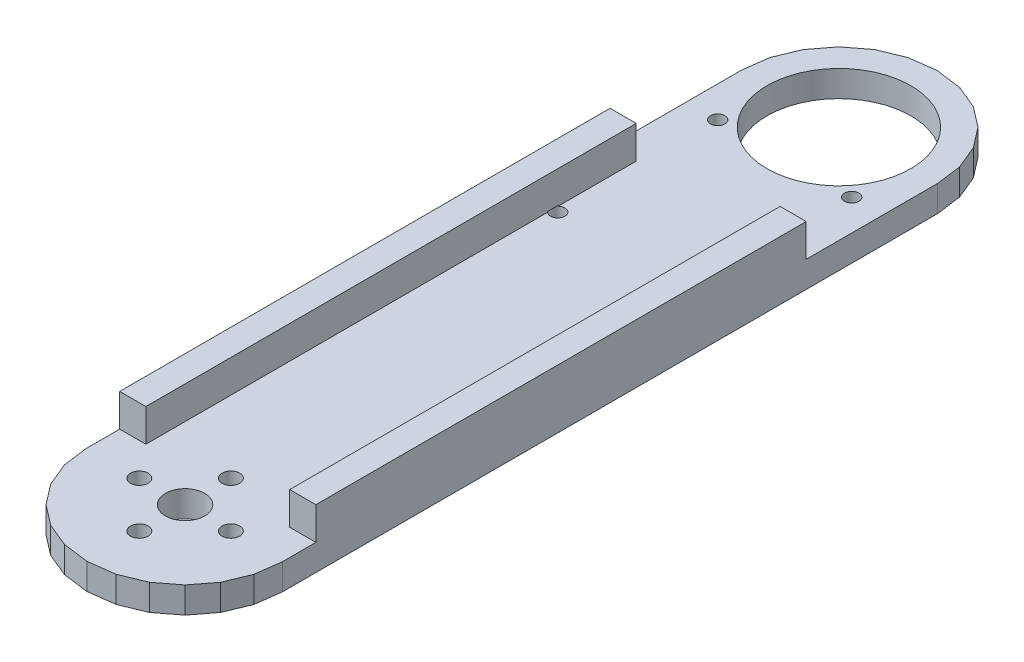
SolidWorks part; units mm, degrees
ref_plane "Front Plane" through (0, 0, 0) normal (0, 0, 1) x (1, 0, 0)
ref_plane "Top Plane" through (0, 0, 0) normal (0, 1, 0) x (1, 0, 0)
ref_plane "Right Plane" through (0, 0, 0) normal (1, 0, 0) x (0, 0, -1)
ref_plane "PY_p18_625" through (0, 18.625, 0) normal (0, 1, 0) x (1, 0, 0)
sketch "S_prism1" plane through (0, 18.625, 0) normal (0, 1, 0) x (1, 0, 0)
  line L0 (-15, -0.1) -> (-14.492, -3.956)
  line L1 (-14.492, -3.956) -> (-13.004, -7.55)
  line L2 (-13.004, -7.55) -> (-10.636, -10.636)
  line L3 (-10.636, -10.636) -> (-7.55, -13.004)
  line L4 (-7.55, -13.004) -> (-3.956, -14.492)
  line L5 (-3.956, -14.492) -> (-0.1, -15)
  line L6 (-0.1, -15) -> (0.1, -15)
  line L7 (0.1, -15) -> (3.956, -14.492)
  line L8 (3.956, -14.492) -> (7.55, -13.004)
  line L9 (7.55, -13.004) -> (10.636, -10.636)
  line L10 (10.636, -10.636) -> (13.004, -7.55)
  line L11 (13.004, -7.55) -> (14.492, -3.956)
  line L12 (14.492, -3.956) -> (15, -0.1)
  line L13 (15, -0.1) -> (15, 100.1)
  line L14 (15, 100.1) -> (14.492, 103.956)
  line L15 (14.492, 103.956) -> (13.004, 107.55)
  line L16 (13.004, 107.55) -> (10.636, 110.636)
  line L17 (10.636, 110.636) -> (7.55, 113.004)
  line L18 (7.55, 113.004) -> (3.956, 114.492)
  line L19 (3.956, 114.492) -> (0.1, 115)
  line L20 (0.1, 115) -> (-0.1, 115)
  line L21 (-0.1, 115) -> (-3.956, 114.492)
  line L22 (-3.956, 114.492) -> (-7.55, 113.004)
  line L23 (-7.55, 113.004) -> (-10.636, 110.636)
  line L24 (-10.636, 110.636) -> (-13.004, 107.55)
  line L25 (-13.004, 107.55) -> (-14.492, 103.956)
  line L26 (-14.492, 103.956) -> (-15, 100.1)
  line L27 (-15, 100.1) -> (-15, -0.1)
  dimension "P1" = 15
  dimension "P2" = 0.1
  dimension "P3" = 14.492
  dimension "P4" = 3.956
  dimension "P5" = 13.004
  dimension "P6" = 7.55
  dimension "P7" = 10.636
  dimension "P8" = 10.636
  dimension "P9" = 7.55
  dimension "P10" = 13.004
  dimension "P11" = 3.956
  dimension "P12" = 14.492
  dimension "P13" = 0.1
  dimension "P14" = 15
  dimension "P15" = 0.1
  dimension "P16" = 15
  dimension "P17" = 3.956
  dimension "P18" = 14.492
  dimension "P19" = 7.55
  dimension "P20" = 13.004
  dimension "P21" = 10.636
  dimension "P22" = 10.636
  dimension "P23" = 13.004
  dimension "P24" = 7.55
  dimension "P25" = 14.492
  dimension "P26" = 3.956
  dimension "P27" = 15
  dimension "P28" = 0.1
  dimension "P29" = 15
  dimension "P30" = 100.1
  dimension "P31" = 14.492
  dimension "P32" = 103.956
  dimension "P33" = 13.004
  dimension "P34" = 107.55
  dimension "P35" = 10.636
  dimension "P36" = 110.636
  dimension "P37" = 7.55
  dimension "P38" = 113.004
  dimension "P39" = 3.956
  dimension "P40" = 114.492
  dimension "P41" = 0.1
  dimension "P42" = 115
  dimension "P43" = 0.1
  dimension "P44" = 115
  dimension "P45" = 3.956
  dimension "P46" = 114.492
  dimension "P47" = 7.55
  dimension "P48" = 113.004
  dimension "P49" = 10.636
  dimension "P50" = 110.636
  dimension "P51" = 13.004
  dimension "P52" = 107.55
  dimension "P53" = 14.492
  dimension "P54" = 103.956
  dimension "P55" = 15
  dimension "P56" = 100.1
extrude "Boss_1" add sketch "S_prism1" along normal blind 4
ref_plane "PZ_m80_000" through (0, 0, -80) normal (0, 0, 1) x (1, 0, 0)
sketch "S_box2" plane through (0, 0, -80) normal (0, 0, 1) x (1, 0, 0)
  line L0 (-15, 22.125) -> (-11, 22.125)
  line L1 (-11, 22.125) -> (-11, 27.625)
  line L2 (-11, 27.625) -> (-15, 27.625)
  line L3 (-15, 27.625) -> (-15, 22.125)
  dimension "P1" = 15
  dimension "P2" = 22.125
  dimension "P3" = 11
  dimension "P4" = 22.125
  dimension "P5" = 11
  dimension "P6" = 27.625
  dimension "P7" = 15
  dimension "P8" = 27.625
extrude "Boss_2" add sketch "S_box2" along normal blind 75
sketch "S_box3" plane through (0, 0, -80) normal (0, 0, 1) x (1, 0, 0)
  line L0 (11, 22.125) -> (15, 22.125)
  line L1 (15, 22.125) -> (15, 27.625)
  line L2 (15, 27.625) -> (11, 27.625)
  line L3 (11, 27.625) -> (11, 22.125)
  dimension "P1" = 11
  dimension "P2" = 22.125
  dimension "P3" = 15
  dimension "P4" = 22.125
  dimension "P5" = 15
  dimension "P6" = 27.625
  dimension "P7" = 11
  dimension "P8" = 27.625
extrude "Boss_3" add sketch "S_box3" along normal blind 75
ref_plane "PY_p18_525" through (0, 18.525, 0) normal (0, 1, 0) x (1, 0, 0)
sketch "S_hole4" plane through (0, 18.525, 0) normal (0, 1, 0) x (1, 0, 0)
  circle A0 centre (0, 0) radius 3
  dimension "D1_S_hole4" = 6
extrude "Hole_4" cut sketch "S_hole4" along normal blind 4.2
sketch "S_hole5" plane through (0, 18.525, 0) normal (0, 1, 0) x (1, 0, 0)
  circle A0 centre (7, 0) radius 1.35
  dimension "D1_S_hole5" = 2.7
  dimension "P2" = 7
extrude "Hole_5" cut sketch "S_hole5" along normal blind 4.2
sketch "S_hole6" plane through (0, 18.525, 0) normal (0, 1, 0) x (1, 0, 0)
  circle A0 centre (0, -7) radius 1.35
  dimension "D1_S_hole6" = 2.7
  dimension "P2" = 7
extrude "Hole_6" cut sketch "S_hole6" along normal blind 4.2
sketch "S_hole7" plane through (0, 18.525, 0) normal (0, 1, 0) x (1, 0, 0)
  circle A0 centre (-7, 0) radius 1.35
  dimension "D1_S_hole7" = 2.7
  dimension "P2" = 7
extrude "Hole_7" cut sketch "S_hole7" along normal blind 4.2
sketch "S_hole8" plane through (0, 18.525, 0) normal (0, 1, 0) x (1, 0, 0)
  circle A0 centre (0, 7) radius 1.35
  dimension "D1_S_hole8" = 2.7
  dimension "P2" = 7
extrude "Hole_8" cut sketch "S_hole8" along normal blind 4.2
sketch "S_hole9" plane through (0, 18.525, 0) normal (0, 1, 0) x (1, 0, 0)
  circle A0 centre (0, 100) radius 11
  dimension "D1_S_hole9" = 22
  dimension "P2" = 100
extrude "Hole_9" cut sketch "S_hole9" along normal blind 4.2
sketch "S_hole10" plane through (0, 18.525, 0) normal (0, 1, 0) x (1, 0, 0)
  circle A0 centre (-10.25, 91.7) radius 1.1
  dimension "D1_S_hole10" = 2.2
  dimension "P2" = 10.25
  dimension "P3" = 91.7
extrude "Hole_10" cut sketch "S_hole10" along normal blind 4.2
sketch "S_hole11" plane through (0, 18.525, 0) normal (0, 1, 0) x (1, 0, 0)
  circle A0 centre (10.25, 91.7) radius 1.1
  dimension "D1_S_hole11" = 2.2
  dimension "P2" = 10.25
  dimension "P3" = 91.7
extrude "Hole_11" cut sketch "S_hole11" along normal blind 4.2
sketch "S_hole12" plane through (0, 18.525, 0) normal (0, 1, 0) x (1, 0, 0)
  circle A0 centre (-10.25, 67.25) radius 1.1
  dimension "D1_S_hole12" = 2.2
  dimension "P2" = 10.25
  dimension "P3" = 67.25
extrude "Hole_12" cut sketch "S_hole12" along normal blind 4.2
sketch "S_hole13" plane through (0, 18.525, 0) normal (0, 1, 0) x (1, 0, 0)
  circle A0 centre (10.25, 67.25) radius 1.1
  dimension "D1_S_hole13" = 2.2
  dimension "P2" = 10.25
  dimension "P3" = 67.25
extrude "Hole_13" cut sketch "S_hole13" along normal blind 4.2
equation "\"plate_t\" = 3"
equation "\"clearance\" = 0.4"
